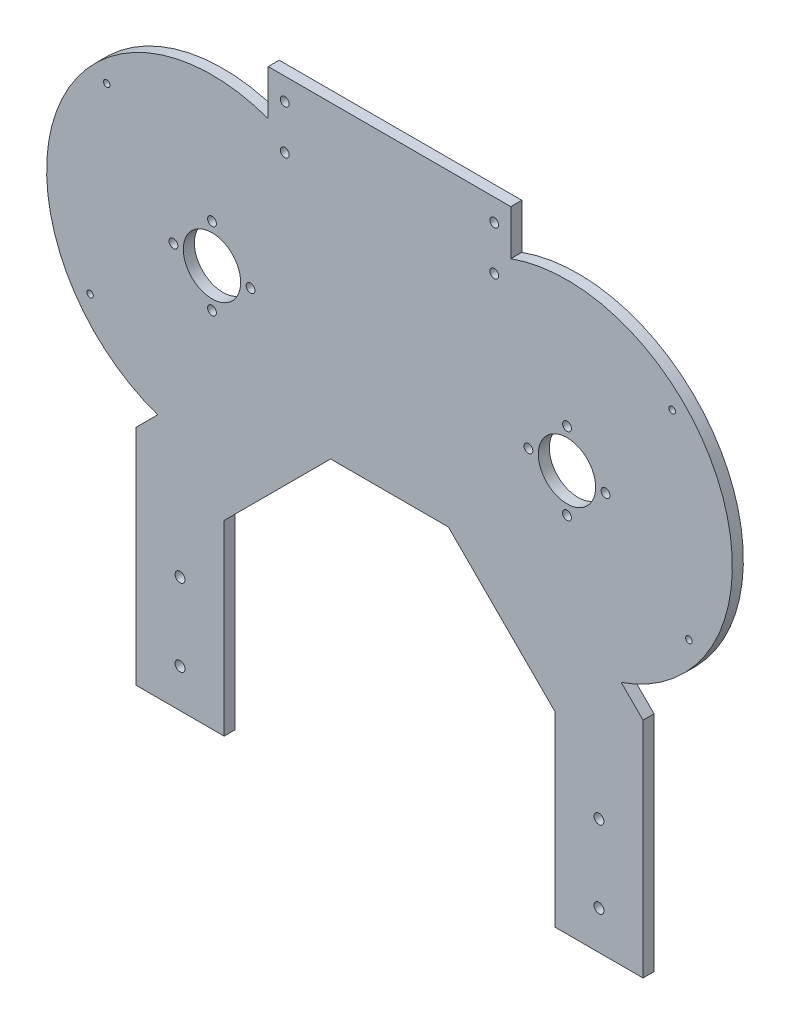
SolidWorks part; units mm, degrees
ref_plane "Front Plane" through (0, 0, 0) normal (0, 0, 1) x (1, 0, 0)
ref_plane "Top Plane" through (0, 0, 0) normal (0, 1, 0) x (1, 0, 0)
ref_plane "Right Plane" through (0, 0, 0) normal (1, 0, 0) x (0, 0, -1)
sketch "Sketch1" plane through (0, 0, 0) normal (0, 0, 1) x (1, 0, 0)
  line L1 (-100, -75) -> (100, -75)
  line L2 (-100, -75) -> (-100, 75)
  line L3 (-100, 75) -> (100, 75)
  line L4 (100, -75) -> (100, 75)
  line L5 (-100, -75) -> (100, 75) construction
  line L6 (-100, 75) -> (100, -75) construction
  line L8 (-47.5, 40) -> (47.5, 40) construction
  line L9 (0, 75) -> (0, -75) construction
  line L10 (-27, -44) -> (27, -44) construction
  line L11 (-27, -44) -> (-27, 28) construction
  line L12 (-27, 28) -> (27, 28) construction
  line L13 (27, -44) -> (27, 28) construction
  line L14 (-27, -44) -> (27, 28) construction
  line L15 (-27, 28) -> (27, -44) construction
  line L23 (-55, 70) -> (55, 70)
  line L24 (-55, 70) -> (-55, -70)
  line L25 (-55, -70) -> (55, -70)
  line L26 (55, 70) -> (55, -70)
  line L27 (-55, 70) -> (55, -70) construction
  line L28 (-55, -70) -> (55, 70) construction
  line L29 (-32.5, 70) -> (32.5, 70) construction
  line L30 (-32.5, 70) -> (-32.5, 55) construction
  line L31 (-32.5, 55) -> (32.5, 55) construction
  line L32 (32.5, 70) -> (32.5, 55) construction
  line L33 (-32.5, 70) -> (32.5, 55) construction
  line L34 (-32.5, 55) -> (32.5, 70) construction
  circle A2 centre (-47.5, 40) radius 2
  circle A3 centre (47.5, 40) radius 2
  circle A4 centre (-27, 28) radius 2 construction
  circle A5 centre (27, 28) radius 2 construction
  circle A6 centre (27, -44) radius 2 construction
  circle A7 centre (-27, -44) radius 2 construction
  circle A8 centre (-47.5, 60) radius 2
  circle A10 centre (47.5, 60) radius 2
  point P0 (0, 0)
  point P15 (0, 40)
  point P18 (0, -8)
  point P56 (0, 0)
  point P63 (0, 62.5)
  dimension "D3" = 4
  dimension "D4" = 20
  dimension "D5" = 4
  dimension "D8" = 4
  dimension "D1" = 150
  dimension "D2" = 200
  dimension "D6" = 72
  dimension "D7" = 54
  dimension "D14" = 30
  dimension "D15" = 140
  dimension "D16" = 110
  dimension "D17" = 95
  dimension "D18" = 12
  dimension "D19" = 15
  dimension "D20" = 65
extrude "Boss-Extrude1" add sketch "Sketch1" along normal blind 5 contours L23 L32 L31 L30 L24 L25 L26 A7 A6 A5 A4 A3 A2 region at (0, -0.1637, 0)
sketch "Sketch2" plane through (0, 0, 0) normal (0, 0, 1) x (1, 0, 0)
  line L0 (-55, -70) -> (-100.8579, -115.8579) construction
  line L1 (-55, 70) -> (-55, -70) construction
  line L2 (-55, -41.7157) -> (-115, -101.7157)
  line L3 (-26.7157, -70) -> (-86.7157, -130)
  line L4 (-55, -70) -> (55, -70) construction
  line L5 (-115, -101.7157) -> (-86.7157, -130)
  line L6 (-115, -101.7157) -> (-115, -203)
  line L7 (-75, -118.2843) -> (-75, -203)
  line L8 (-75, -203) -> (-115, -203)
  line L9 (0, 75) -> (0, -75) construction
  line L10 (-55, -41.7157) -> (-26.7157, -70)
  line L11 (-55, 70) -> (-55, -70) construction
  line L12 (-115, -203) -> (-75, -203) construction
  circle A0 centre (-95, -150.5) radius 2.25
  circle A1 centre (-95, -185.5) radius 2.25
  circle A2 centre (-95, -150.5) radius 2.25 construction
  circle A4 centre (-95, -185.5) radius 2.25 construction
  dimension "D1" = 135
  dimension "D2" = 40
  dimension "D3" = 40
  dimension "D4" = 75
  dimension "D5" = 0
extrude "Boss-Extrude2" add sketch "Sketch2" along normal blind 5 contours L8 L7 L3 L5 L6 | L10 L2 L5 L3 region at (-70.8579, -85.8579, 0) region at (-95.9307, -160.1869, 0)
mirror "Mirror1" about plane through (0, 0, 0) normal (1, 0, 0) of "Boss-Extrude2"
sketch "Sketch3" plane through (0, 0, 5) normal (0, 0, 1) x (1, 0, 0)
  line L0 (0, 31.3301) -> (0, 52.1198) construction
  line L1 (-80.5, -21) -> (-128.2297, 26.7297) construction
  line L2 (-80.5, -21) -> (80.5, -21) construction
  line L3 (-80.5, -21) -> (-148, -21) construction
  line L4 (-80.5, -21) -> (-135.7928, -59.7164) construction
  circle A0 centre (-80.5, -21) radius 75
  circle A1 centre (-80.5, -3.5) radius 2
  circle A2 centre (80.5, -21) radius 75
  circle A3 centre (-80.5, -21) radius 60
  circle A4 centre (80.5, -21) radius 60
  circle A5 centre (-47.5, 40) radius 2 construction
  circle A6 centre (-47.5, 40) radius 2
  circle A7 centre (47.5, 40) radius 2
  circle A8 centre (-63, -21) radius 2
  circle A9 centre (-80.5, -38.5) radius 2
  circle A10 centre (-98, -21) radius 2
  circle A11 centre (98, -21) radius 2
  circle A12 centre (80.5, -38.5) radius 2
  circle A13 centre (63, -21) radius 2
  circle A14 centre (80.5, -3.5) radius 2
  circle A15 centre (-80.5, -21) radius 13
  circle A16 centre (80.5, -21) radius 13
  circle A17 centre (-128.2297, 26.7297) radius 1.4732
  circle A18 centre (-135.7928, -59.7164) radius 1.4732
  circle A19 centre (-80.5, -21) radius 67.5 construction
  circle A20 centre (128.2297, 26.7297) radius 1.4732
  circle A21 centre (135.7928, -59.7164) radius 1.4732
  point P28 (-80.5, -21)
  line M3 (115, -101.7157) -> (55, -41.7157)
  line M4 (55, -41.7157) -> (55, 70)
  line M6 (-55, 70) -> (-55, -41.7157)
  line M7 (-55, -41.7157) -> (-115, -101.7157)
  line M11 (-75, -118.2843) -> (-26.7157, -70)
  line M12 (-26.7157, -70) -> (26.7157, -70)
  line M13 (26.7157, -70) -> (75, -118.2843)
  circle M17 centre (-47.5, 40) radius 2
  circle M18 centre (47.5, 40) radius 2
  dimension "D1" = 161
  dimension "D2" = 150
  dimension "D3" = 61
  dimension "D4" = 120
  dimension "D5" = 4
  dimension "D7" = 35
  dimension "D8" = 26
  dimension "D9" = 7.5
  dimension "D10" = 2.9464
  dimension "D6" = 4
  dimension "D11" = 45
  dimension "D12" = 35
extrude "Boss-Extrude3" add sketch "Sketch3" against normal up to surface (5 mm away) contours A3 M6 M7 | A3 A0 M6 M7 | A3 A0 M7 M11 M12 M6 M17 | A3 M7 M6 | A4 M3 M4 | A4 M4 M3 | A4 A2 M4 M3 | A4 A2 M3 M4 M12 M13 M18 region at (-11.8554, -46.5242, 5) region at (9.6495, -2.4591, 5) region at (-56.7712, 41.4218, 5) region at (-96.2806, -16.4848, 5) region at (-46.5969, -30.7004, 5) region at (122.5668, 38.9404, 5) region at (46.5969, -30.7004, 5) region at (96.2806, -16.4848, 5) up to face at (0, -95.388, 0)
